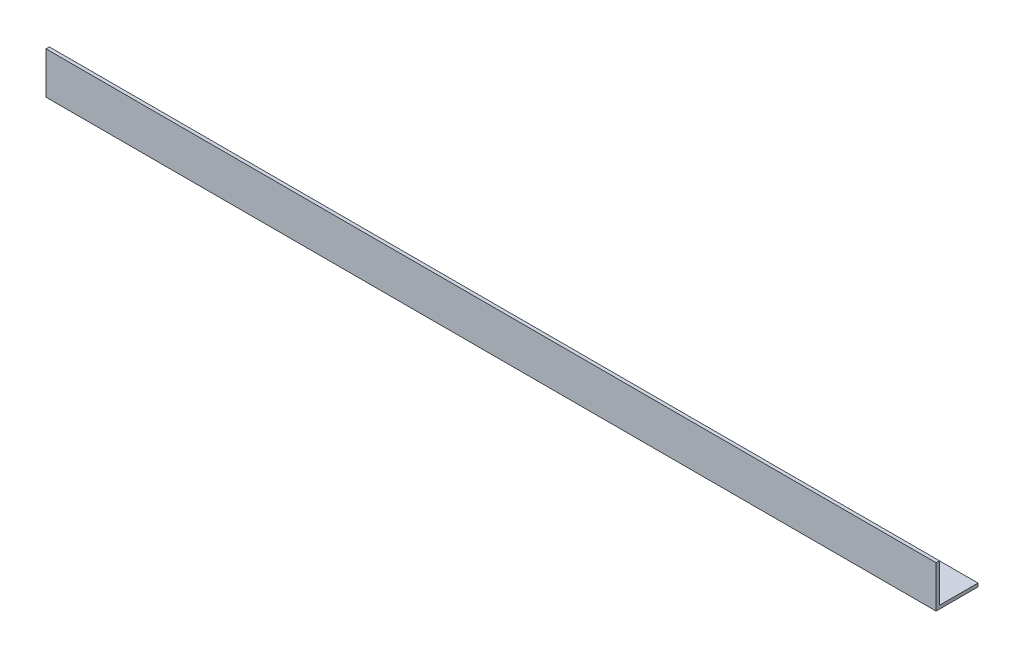
SolidWorks part; units mm, degrees
ref_plane "Спереди" through (0, 0, 0) normal (0, 0, 1) x (1, 0, 0)
ref_plane "Сверху" through (0, 0, 0) normal (0, 1, 0) x (1, 0, 0)
ref_plane "Справа" through (0, 0, 0) normal (1, 0, 0) x (0, 0, -1)
sketch "Эскиз1" plane through (0, 0, 0) normal (1, 0, 0) x (0, 0, -1)
  line L0 (0, 25) -> (0, 0)
  line L1 (0, 0) -> (25, 0)
extrude "Вытянуть-Тонкостенный1" add sketch "Эскиз1" along normal blind 531 thin thin type one direction reverse wall 2
